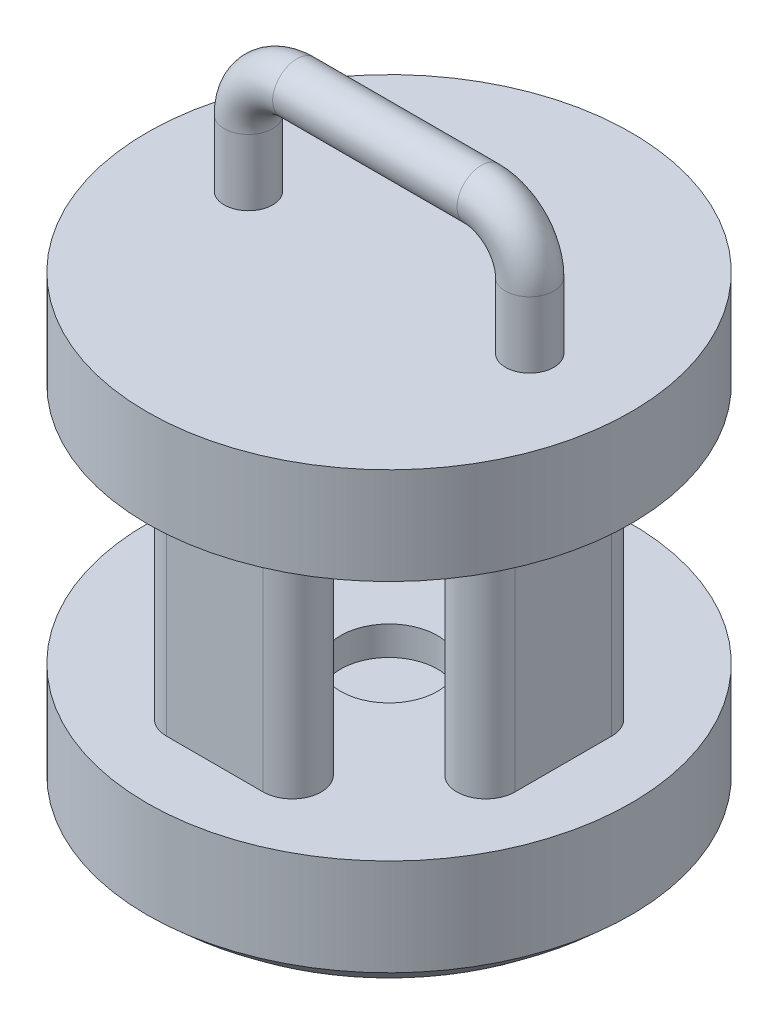
SolidWorks part; units mm, degrees
ref_plane "Front Plane" through (0, 0, 0) normal (0, 0, 1) x (1, 0, 0)
ref_plane "Top Plane" through (0, 0, 0) normal (0, 1, 0) x (1, 0, 0)
ref_plane "Right Plane" through (0, 0, 0) normal (1, 0, 0) x (0, 0, -1)
sketch "Sketch1" plane through (0, 0, 0) normal (0, 1, 0) x (1, 0, 0)
  circle A0 centre (0, 0) radius 6.35
  dimension "D1" = 12.7
extrude "button" add sketch "Sketch1" along normal blind 2.54
ref_axis "central axis" through (0, 2.54, 0) along (0, -1, 0)
sketch "Sketch2" plane through (0, 2.54, 0) normal (0, 1, 0) x (1, 0, 0)
  line L0 (-1.27, -3.81) -> (1.27, -3.81) construction
  line L1 (-1.27, -3.048) -> (1.27, -3.048)
  line L2 (-1.27, -4.572) -> (1.27, -4.572)
  arc A0 (-1.27, -3.048) -> (-1.27, -4.572) centre (-1.27, -3.81) ccw
  arc A1 (1.27, -4.572) -> (1.27, -3.048) centre (1.27, -3.81) ccw
  point P2 (0, -3.81)
  dimension "D2" = 0.762
  dimension "D1" = 2.54
  dimension "D3" = 0
  dimension "D4" = 3.81
extrude "one leg" add sketch "Sketch2" along normal blind 6.35
pattern_circular "moar legs" count 4 over 360 about axis through (0, 2.54, 0) along (0, -1, 0) of "one leg"
sketch "Sketch3" plane through (0, 8.89, 0) normal (0, 1, 0) x (1, 0, 0)
  circle A0 centre (0, 0) radius 6.35
extrude "button bottom" add sketch "Sketch3" along normal blind 2.54
dome "button top" faces to dome 1 distance 2.54 reverse direction no elliptical dome no face at (0, 0, 6.35) parameters "D1"=2.54
sketch "Sketch4" plane through (0, 0, 0) normal (0, 0, 1) x (1, 0, 0)
  line L1 (0, 11.43) -> (0, 15.4488) construction
  line L4 (-3.6897, 11.43) -> (-3.6897, 13.1638)
  line L5 (6.35, 11.43) -> (-6.35, 11.43) construction
  line L6 (-2.4197, 14.4338) -> (2.4197, 14.4338)
  line L7 (3.6897, 11.43) -> (3.6897, 13.1638)
  arc A0 (3.6897, 13.1638) -> (2.4197, 14.4338) centre (2.4197, 13.1638) ccw
  arc A1 (-3.6897, 13.1638) -> (-2.4197, 14.4338) centre (-2.4197, 13.1638) cw
  point P10 (0, 14.4338)
  point P12 (3.6897, 14.4338)
  point P15 (-3.6897, 14.4338)
  dimension "D1" = 1.27
sketch "Sketch5" plane through (0, 11.43, 0) normal (0, 1, 0) x (1, 0, 0)
  circle A0 centre (-3.6897, 0) radius 0.635
  dimension "D1" = 1.27
sweep "handle for linkage" add profiles "Sketch5" path "Sketch4"
sketch "Sketch6" plane through (0, 2.54, 0) normal (0, 1, 0) x (1, 0, 0)
  circle A0 centre (0, 0) radius 1.27
  dimension "D1" = 2.54
extrude "recess for spring" cut sketch "Sketch6" against normal blind 0.762
